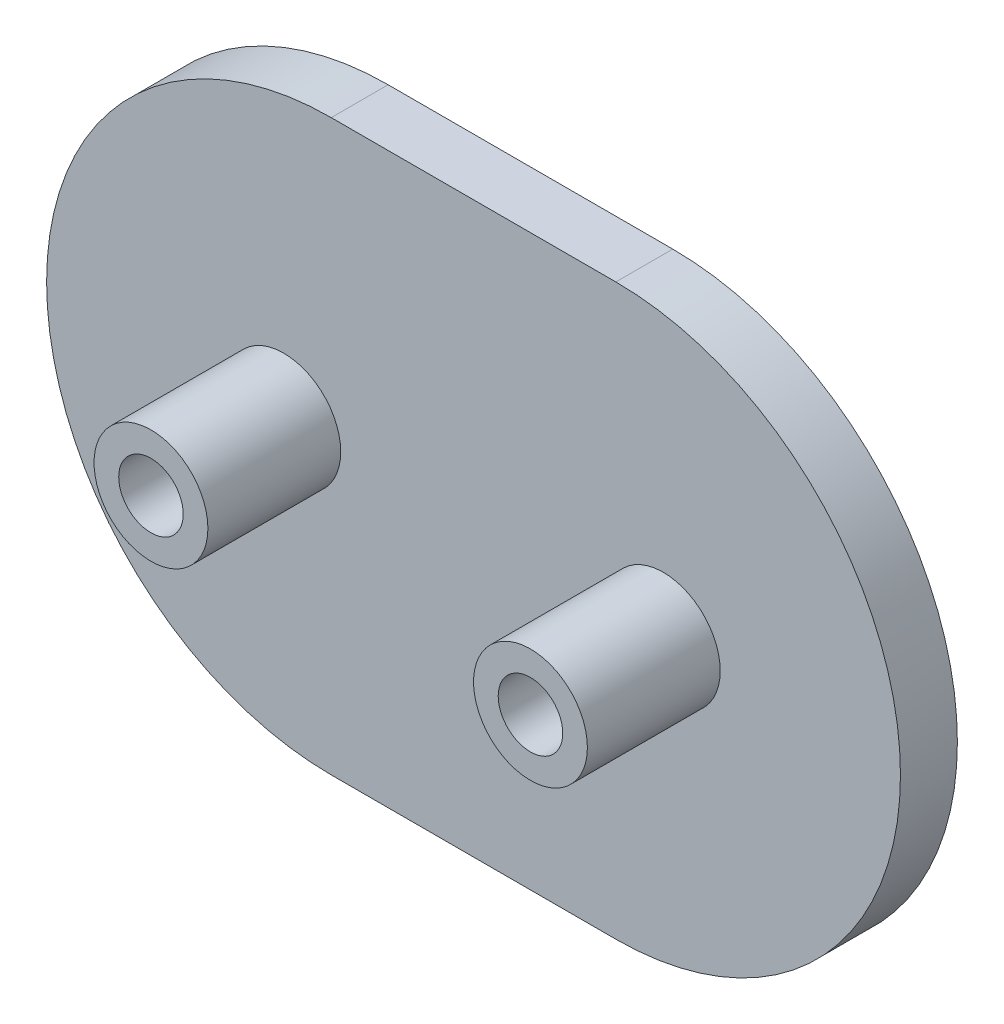
SolidWorks part; units mm, degrees
ref_plane "前视基准面" through (0, 0, 0) normal (0, 0, 1) x (1, 0, 0)
ref_plane "上视基准面" through (0, 0, 0) normal (0, 1, 0) x (1, 0, 0)
ref_plane "右视基准面" through (0, 0, 0) normal (1, 0, 0) x (0, 0, -1)
sketch "草图1" plane through (0, 0, 0) normal (0, 0, 1) x (1, 0, 0)
  line L0 (-7.5, 0) -> (7.5, 0) construction
  line L1 (-7.5, 15) -> (7.5, 15)
  line L2 (-7.5, -15) -> (7.5, -15)
  arc A0 (-7.5, 15) -> (-7.5, -15) centre (-7.5, 0) ccw
  arc A1 (7.5, -15) -> (7.5, 15) centre (7.5, 0) ccw
  circle A3 centre (-10, 0) radius 3
  circle A4 centre (10, 0) radius 3
  circle A6 centre (-10, 0) radius 1.7
  circle A7 centre (10, 0) radius 1.7
  point P3 (0, 0)
  dimension "D1" = 15
  dimension "D3" = 3.4
  dimension "D4" = 3.4
  dimension "D5" = 6
  dimension "D6" = 10
  dimension "D7" = 10
  dimension "D2" = 15
extrude "凸台-拉伸1" add sketch "草图1" along normal blind 3 contours L2 A1 L1 A0 A4 A3 region at (0, 0, 0)
extrude "凸台-拉伸2" add sketch "草图1<3>" along normal blind 10 contours A3 A6 | A4 A7 region at (-12.9151, 0, 0) region at (7.0849, 0, 0)
sketch "草图1<3>" plane through (0, 0, 0) normal (0, 0, 1) x (1, 0, 0) same geometry as "草图1"
chamfer "倒角1" distance 1.4 angle 45 2 edges at (11.7, 0, 0) (-8.3, 0, 0)
